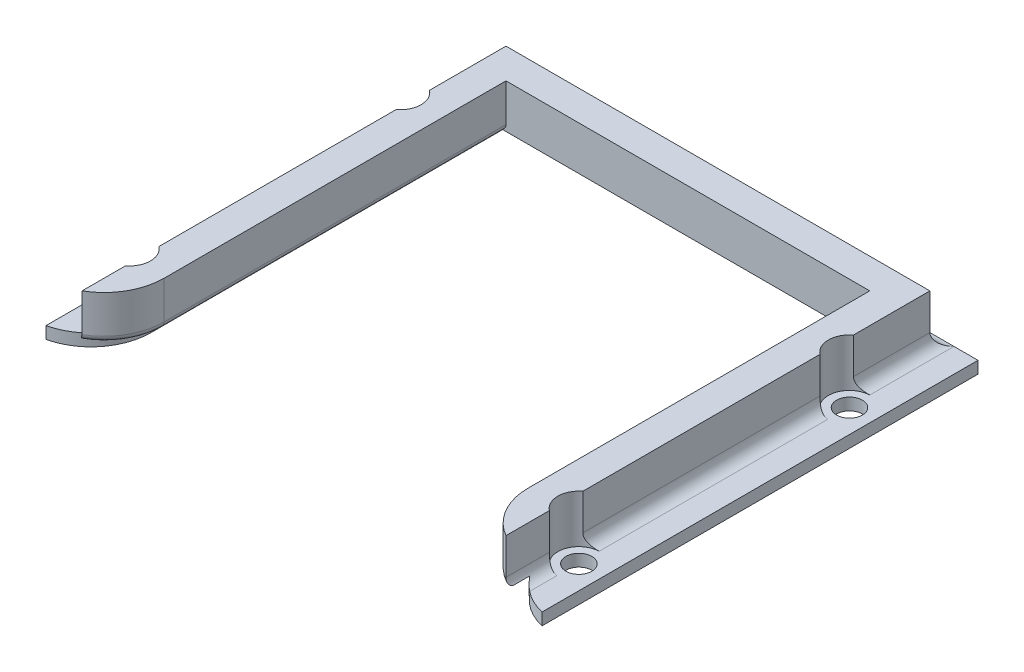
SolidWorks part; units mm, degrees
material "PLA+"
ref_plane "Front Plane" through (0, 0, 0) normal (0, 0, 1) x (1, 0, 0)
ref_plane "Top Plane" through (0, 0, 0) normal (0, 1, 0) x (1, 0, 0)
ref_plane "Right Plane" through (0, 0, 0) normal (1, 0, 0) x (0, 0, -1)
sketch "Sketch1" plane through (0, 0, 0) normal (0, 1, 0) x (1, 0, 0)
  line L0 (35.25, 35.25) -> (35.25, -35.25)
  line L1 (30.25, 30.25) -> (-30.25, 30.25)
  line L2 (30.25, 30.25) -> (30.25, -30.25)
  line L3 (30.25, -30.25) -> (-30.25, -30.25)
  line L4 (-30.25, 30.25) -> (-30.25, -30.25)
  line L5 (30.25, 30.25) -> (-30.25, -30.25) construction
  line L6 (30.25, -30.25) -> (-30.25, 30.25) construction
  line L7 (35.25, -35.25) -> (-35.25, -35.25)
  line L8 (-35.25, 35.25) -> (-35.25, -35.25)
  line L9 (35.25, 35.25) -> (-35.25, 35.25)
  point P0 (0, 0)
  dimension "D1" = 60.5
  dimension "D2" = 60.5
  dimension "D3" = 5
extrude "Boss-Extrude1" add sketch "Sketch1" along normal blind 10 contours L0 L9 L8 L7 L4 L1 L2 L3 region at (34.253, 0, 0)
sketch "Sketch2" plane through (0, 0, 35.25) normal (0, 0, 1) x (1, 0, 0)
  line L0 (35.25, 0) -> (-35.25, 0) construction
  line L1 (33.5, -2.7) -> (-33.5, -2.7)
  line L2 (33.5, -2.7) -> (33.5, 2.7)
  line L3 (33.5, 2.7) -> (-33.5, 2.7)
  line L4 (-33.5, -2.7) -> (-33.5, 2.7)
  line L5 (33.5, -2.7) -> (-33.5, 2.7) construction
  line L6 (33.5, 2.7) -> (-33.5, -2.7) construction
  point P0 (0, 0)
  dimension "D1" = 2.7
  dimension "D2" = 67
extrude "Cut-Extrude1" cut sketch "Sketch2" against normal blind 70
sketch "Sketch6" plane through (0, 0, 0) normal (0, -1, 0) x (1, 0, 0)
  line L0 (-35.25, -35.25) -> (-35.25, 35.25) construction
  line L1 (41.25, 37.25) -> (-41.25, 37.25)
  line L2 (41.25, 37.25) -> (41.25, -37.25)
  line L3 (41.25, -37.25) -> (-41.25, -37.25)
  line L4 (-41.25, 37.25) -> (-41.25, -37.25)
  line L5 (41.25, 37.25) -> (-41.25, -37.25) construction
  line L6 (41.25, -37.25) -> (-41.25, 37.25) construction
  line L7 (35.25, -35.25) -> (-35.25, -35.25) construction
  line L9 (-35.25, -35.25) -> (35.25, -35.25)
  line L10 (-35.25, -35.25) -> (-35.25, 47.3198)
  line L11 (-35.25, 47.3198) -> (35.25, 47.3198)
  line L12 (35.25, -35.25) -> (35.25, 47.3198)
  point P0 (0, 0)
  line M8 (-35.25, 35.25) -> (-35.25, -35.25)
  line M9 (-35.25, -35.25) -> (35.25, -35.25)
  line M10 (35.25, -35.25) -> (35.25, 35.25)
  dimension "D1" = 6
  dimension "D2" = 2
extrude "Boss-Extrude3" add sketch "Sketch6" against normal blind 2 contours L12 L10 L1 L4 L3 L2 M10 M9 M8 region at (40.1384, 0, 0)
sketch "Sketch7" plane through (0, 2.7, 0) normal (0, -1, 0) x (1, 0, 0)
  line L0 (33.5, 35.25) -> (-33.5, 35.25) construction
  line L1 (-30.25, 30.25) -> (30.25, 30.25)
  line L2 (-30.25, 30.25) -> (-30.25, 35.25)
  line L3 (-30.25, 35.25) -> (30.25, 35.25)
  line L4 (30.25, 30.25) -> (30.25, 35.25)
extrude "Cut-Extrude3" cut sketch "Sketch7" against normal blind 25
fillet "Fillet2" radius 2 3 edges at (35.25, 2, 0) (0, 2, -35.25) (-35.25, 2, 0)
sketch "Sketch8" plane through (0, 0, 37.25) normal (0, 0, 1) x (1, 0, 0)
  line L1 (-54.512, 19.9727) -> (42.871, 19.9727)
  line L2 (-54.512, 19.9727) -> (-54.512, -15.1108)
  line L3 (-54.512, -15.1108) -> (42.871, -15.1108)
  line L4 (42.871, 19.9727) -> (42.871, -15.1108)
extrude "Cut-Extrude4" cut sketch "Sketch8" against normal blind 2 contours L2 L1 L4 L3
sketch "Sketch9" plane through (0, 0, 0) normal (0, -1, 0) x (1, 0, 0)
  line L0 (-33.5, 35.25) -> (-41.25, 35.25) construction
  line L1 (0, -5.5) -> (0, 5.5) construction
  circle A0 centre (-37.375, 25.25) radius 2.15
  circle A1 centre (-37.375, -19.75) radius 2.15
  circle A2 centre (37.375, -19.75) radius 2.15
  circle A3 centre (37.375, 25.25) radius 2.15
  point P7 (-37.375, 35.25)
  dimension "D1" = 4.3
  dimension "D2" = 4.3
  dimension "D3" = 55
  dimension "D4" = 10
extrude "Cut-Extrude5" cut sketch "Sketch9" against normal mid plane 10
sketch "Sketch10" plane through (0, 10, 0) normal (0, 1, 0) x (1, 0, 0)
  line L0 (0, -5.5) -> (0, 5.5) construction
  circle A0 centre (-37.375, 19.75) radius 3.5
  circle A1 centre (-37.375, -25.25) radius 3.5
  circle A2 centre (37.375, -25.25) radius 3.5
  circle A3 centre (37.375, 19.75) radius 3.5
  dimension "D1" = 7
  dimension "D2" = 7
extrude "Cut-Extrude6" cut sketch "Sketch10" against normal blind 8
fillet "Fillet3" radius 10 2 edges at (-33.5, 1.35, 35.25) (33.5, 1.35, 35.25)
fillet "Fillet4" radius 10 2 edges at (30.25, 6.35, 35.25) (-30.25, 6.35, 35.25)
fillet "Fillet5" radius 1 4 edges at (30.25, 2.7, -1.8301) (-30.25, 2.7, -1.8301) (31.5897, 2.7, 31.5897) (-31.5897, 2.7, 31.5897)
